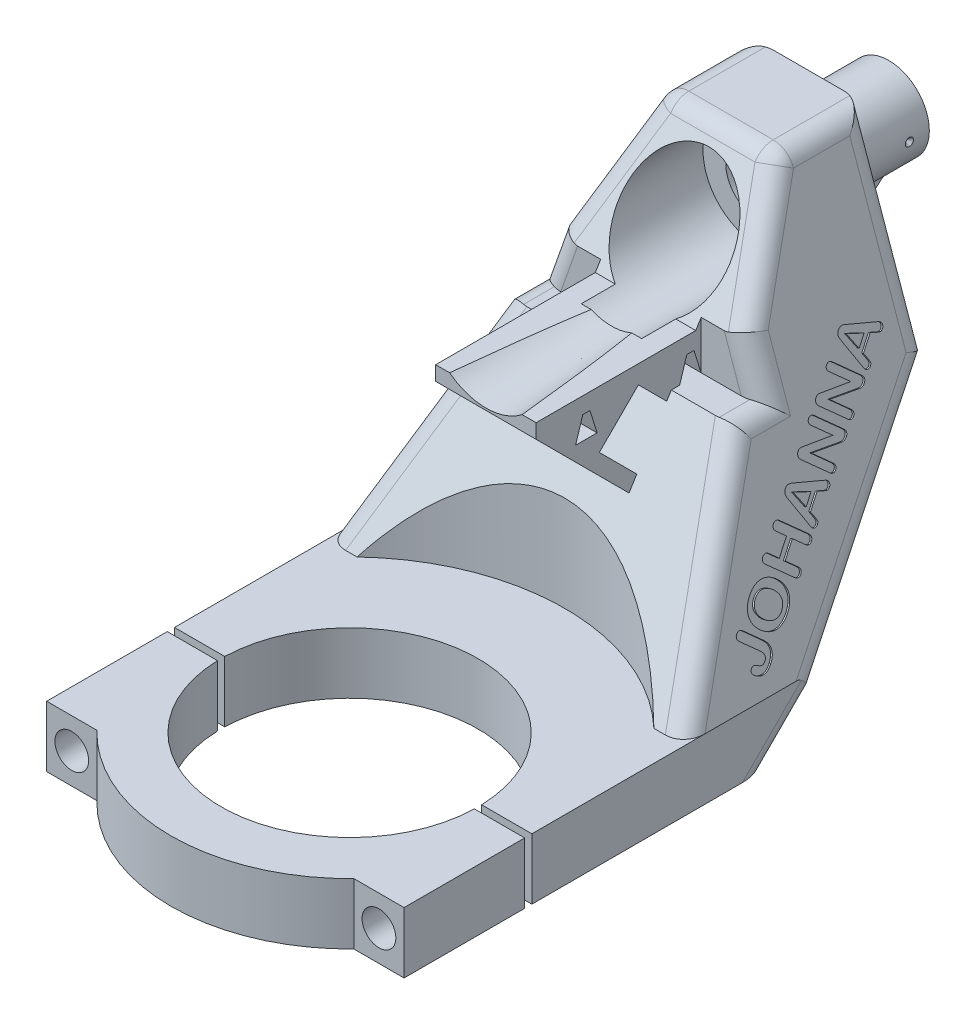
SolidWorks part; units mm, degrees
ref_plane "Front Plane" through (0, 0, 0) normal (0, 0, 1) x (1, 0, 0)
ref_plane "Top Plane" through (0, 0, 0) normal (0, 1, 0) x (1, 0, 0)
ref_plane "Right Plane" through (0, 0, 0) normal (1, 0, 0) x (0, 0, -1)
ref_plane "kitchenaid front" through (0, 0, -128) normal (0, 0, 1) x (1, 0, 0)
ref_plane "jar clamp bottom" through (0, -92.83, 0) normal (0, 1, 0) x (1, 0, 0)
sketch "Sketch1" plane through (0, -92.83, 0) normal (0, 1, 0) x (1, 0, 0)
  line L0 (49.81, -34.622) -> (49.81, 0)
  line L1 (49.81, -34.622) -> (35.81, -34.622)
  line L2 (0, -49.81) -> (0, -35.81)
  line L3 (49.81, 0) -> (49.81, 128)
  line L4 (0, 35.81) -> (0, 128)
  line L5 (0, 128) -> (49.81, 128)
  line L6 (35.81, 0) -> (35.81, -34.622) construction
  line L7 (-54.791, 128) -> (54.791, 128) construction
  arc A0 (0, -35.81) -> (0, 35.81) centre (0, 0) ccw
  arc A2 (49.81, 0) -> (0, 49.81) centre (0, 0) ccw construction
  arc A5 (35.81, -34.622) -> (49.81, 0) centre (0, 0) ccw construction
  arc A6 (35.81, -34.622) -> (49.81, 0) centre (0, 0) ccw construction
  arc A7 (0, -49.81) -> (35.81, -34.622) centre (0, 0) ccw
  dimension "D1" = 71.62
  dimension "D2" = 14
extrude "Boss-Extrude1" add sketch "Sketch1" along normal blind 17
ref_plane "Plane3" through (42.81, 0, 0) normal (1, 0, 0) x (0, 0, -1)
ref_plane "Plane4" through (0, -84.33, 0) normal (0, 1, 0) x (1, 0, 0)
ref_axis "Axis2" through (42.81, -84.33, -0.6811) along (0, 0, 1)
sketch "Sketch6" plane through (42.81, 0, 0) normal (1, 0, 0) x (0, 0, -1)
  line L0 (-34.622, -79.63) -> (-6, -79.63)
  line L1 (-34.622, -75.83) -> (-34.622, -92.83) construction
  line L2 (-6, -79.63) -> (-6, -82.13)
  line L3 (-6, -82.13) -> (-1, -82.13)
  line L4 (2, -82.13) -> (2, -82.73) construction
  line L5 (2, -82.73) -> (22, -82.73)
  line L6 (22, -82.73) -> (22, -84.33)
  line L7 (27.3955, -84.33) -> (-27.3955, -84.33) construction
  line L8 (22, -84.33) -> (-34.622, -84.33)
  line L9 (-34.622, -84.33) -> (-34.622, -79.63)
  line L10 (1, -82.13) -> (1, -64.33)
  line L11 (1, -64.33) -> (-1, -64.33)
  line L12 (-1, -64.33) -> (-1, -82.13)
  line L13 (-1, -82.13) -> (1, -82.13) construction
  line L14 (1, -82.13) -> (2, -82.13) construction
  line L16 (0, 9.35) -> (0, -9.35) construction
  line L17 (1, -82.13) -> (1, -82.73)
  line L18 (1, -82.73) -> (2, -82.73)
  point P18 (0, -64.33)
  dimension "D1" = 4.7
  dimension "D2" = 2.2
  dimension "D3" = 1.6
  dimension "D4" = 20
  dimension "D5" = 5
  dimension "D6" = 2
  dimension "D7" = 1
  dimension "D8" = 20
revolve "Cut-Revolve3" cut sketch "Sketch6" angle 360 about axis through (42.81, -84.33, -0.6811) along (0, 0, 1)
sketch "Sketch2" plane through (0, -92.83, 0) normal (0, 1, 0) x (1, 0, 0)
  line L0 (49.81, -34.622) -> (49.81, -1) construction
  line L1 (0, 128) -> (0, 35.81) construction
  line L2 (0, 60) -> (0, 128)
  line L3 (-9.35, 128) -> (9.35, 128) construction
  line L4 (0, 128) -> (49.81, 128)
  line L5 (49.81, 128) -> (49.81, 33.4509)
  arc A0 (49.81, 33.4509) -> (0, 60) centre (0, 0) ccw
  dimension "D1" = 60
extrude "Boss-Extrude2" add sketch "Sketch2" along normal offset from surface (112.83 mm away) 20 up to plane "Top Plane" offset beyond the face yes
sketch "Sketch3" plane through (0, 0, -128) normal (0, 0, 1) x (1, 0, 0)
  line L0 (0, 11.3) -> (0, 9.15)
  line L1 (0, 9.15) -> (0, -9.15) construction
  line L2 (0, -9.15) -> (0, -11.3)
  arc A0 (0, -11.3) -> (0, 11.3) centre (0, 0) ccw
  arc A1 (0, -9.15) -> (0, 9.15) centre (0, 0) ccw
  arc A2 (0, 11.3) -> (0, -11.3) centre (0, 0) ccw construction
  arc A3 (0, 9.15) -> (0, -9.15) centre (0, 0) ccw construction
  dimension "D1" = 18.3
  dimension "D2" = 22.6
extrude "Boss-Extrude3" add sketch "Sketch3" against normal blind 22.3
sketch "Sketch11" plane through (0, 0, 0) normal (1, 0, 0) x (0, 0, -1)
  line L0 (-49.6786, -34.03) -> (55, -34.03) construction
  line L1 (55, -34.03) -> (55, -92.83) construction
  line L2 (27.3955, -92.83) -> (-27.3955, -92.83) construction
  line L3 (63.7273, -13) -> (34.47, -13)
  line L5 (34.47, -13) -> (34.47, -13.5)
  line L6 (34.47, -13.5) -> (64.1074, -43.1374)
  line L8 (64.1074, -43.1374) -> (70.3979, -33.1815)
  line L9 (70.3979, -33.1815) -> (63.7273, -26.5109)
  line L11 (63.7273, -26.5109) -> (63.7273, -13)
  dimension "D1" = 58.8
  dimension "D2" = 55
  dimension "D3" = 45
  dimension "D4" = 0.5
extrude "Boss-Extrude6" add sketch "Sketch11" along normal up to surface (49.81 mm away) up to face at (49.81, -49.5533, -54.1503)
ref_axis "Axis1" through (0, 0, 59.6655) along (0, 0, -1)
sketch "Sketch4" plane through (0, 0, 0) normal (1, 0, 0) x (0, 0, -1)
  line L0 (114, 9.15) -> (114, 11.5)
  line L1 (-59.6655, 0) -> (157.1555, 0) construction
  line L2 (114, 11.5) -> (-16, 20)
  line L3 (-16, 20) -> (-16, 0)
  line L4 (-16, 0) -> (114, 0)
  line L5 (128, 27.3955) -> (128, -27.3955) construction
  line L6 (114, 9.15) -> (128, 9.15)
  line L7 (128, 9.15) -> (128, 0)
  line L8 (128, 0) -> (114, 0)
  line L9 (114, 0) -> (114, 9.15) construction
  dimension "D1" = 11.5
  dimension "D2" = 20
  dimension "D3" = 16
  dimension "D4" = 14
  dimension "D5" = 9.15
revolve "Cut-Revolve1" cut sketch "Sketch4" angle 360 about axis through (0, 0, 59.6655) along (0, 0, -1)
sketch "Sketch5" plane through (0, 0, 0) normal (1, 0, 0) x (0, 0, -1)
  line L0 (43.4509, -75.83) -> (63.897, -42.927)
  line L1 (33.4509, 20) -> (128, 20) construction
  line L2 (103, 20) -> (33.4509, 20)
  line L3 (33.4509, 20) -> (33.4509, -75.83)
  line L4 (33.4509, -75.83) -> (43.4509, -75.83)
  line L5 (128, 54.791) -> (128, -54.791) construction
  line L6 (1, -75.83) -> (33.4509, -75.83) construction
  line L7 (68.17, -92.83) -> (128, -33)
  line L8 (54.791, -92.83) -> (-54.791, -92.83) construction
  line L9 (128, -33) -> (128, -92.83)
  line L10 (128, -92.83) -> (68.17, -92.83)
  line L11 (38, -13) -> (82.4937, -13)
  line L12 (38, -13) -> (38, -17.03)
  line L13 (38, -17.03) -> (63.897, -42.927)
  line L14 (51, -17.5538) -> (49, -23.9536)
  line L15 (49, -23.9536) -> (55, -23.9536)
  line L16 (55, -23.9536) -> (53, -17.5538)
  line L17 (80, -17.5538) -> (78, -23.9536)
  line L18 (78, -23.9536) -> (84, -23.9536)
  line L19 (84, -23.9536) -> (82, -17.5538)
  line L20 (-59.6655, 0) -> (157.1555, 0) construction
  line L21 (63.897, -42.927) -> (82.4937, -13) construction
  line L22 (82.4937, -13) -> (103, 20)
  line L23 (52, -14.354) -> (81, -14.354) construction
  line L24 (37.4736, -16.5036) -> (60, -39.03) construction
  line L25 (52, -17.5538) -> (52, -23.9536) construction
  line L26 (52, -14.354) -> (52, -15.5538) construction
  line L27 (81, -17.5538) -> (81, -23.9536) construction
  line L28 (114, -11.5) -> (37.4736, -16.5036) construction
  line L29 (51, -17.5538) -> (53, -17.5538)
  line L30 (79.6639, -17.5538) -> (80, -17.5538) construction
  line L31 (80, -17.5538) -> (82, -17.5538)
  line L32 (53, -17.5538) -> (79.6639, -17.5538) construction
  line L33 (53, -17.5538) -> (52, -14.354) construction
  line L34 (52, -14.354) -> (52, -17.5538) construction
  line L35 (52, -14.354) -> (51, -17.5538) construction
  line L36 (82, -17.5538) -> (81, -14.354) construction
  line L37 (81, -14.354) -> (81, -17.5538) construction
  line L38 (81, -14.354) -> (80, -17.5538) construction
  line L39 (66.065, -39.4381) -> (55.6186, -28.9918)
  line L40 (55.6186, -28.9918) -> (66.5, -18.1104)
  line L41 (66.5, -18.1104) -> (74.4055, -26.0159)
  line L42 (74.4055, -26.0159) -> (66.065, -39.4381)
  dimension "D1" = 10
  dimension "D2" = 25
  dimension "D3" = 45
  dimension "D4" = 33
  dimension "D5" = 13
  dimension "D6" = 38
  dimension "D7" = 14
  dimension "D8" = 2
  dimension "D9" = 6
  dimension "D10" = 6
  dimension "D11" = 43
  dimension "D12" = 2
  dimension "D13" = 4
  dimension "D14" = 4
  dimension "D15" = 45
  dimension "D16" = 4
extrude "Cut-Extrude1" cut sketch "Sketch5" along normal through all
ref_plane "Plane7" through (0, 0, -53) normal (0, 0, 1) x (1, 0, 0)
sketch "Sketch16" plane through (0, 0, -53) normal (0, 0, 1) x (1, 0, 0)
  circle A0 centre (0, 0) radius 15.4885
  point P3 (0, -15.4885)
  point P7 (0, 0)
extrude "Cut-Extrude7" cut sketch "Sketch16" against normal up to surface (61 mm away) from offset 20 up to face at (5.1625, 0, -114) offset against normal yes
fillet "Fillet1" [suppressed] radius 5
sketch "Sketch7" plane through (0, 0, 0) normal (1, 0, 0) x (0, 0, -1)
  line L0 (130, -12.3) -> (130, -9.15)
  line L1 (130, -9.15) -> (150.3, -9.15)
  line L2 (150.3, -9.15) -> (128, -27.8619)
  line L3 (128, 54.791) -> (128, -54.791) construction
  line L4 (128, -27.8619) -> (128, -18.9782)
  line L5 (128, -18.9782) -> (130, -17.3)
  line L6 (130, -17.3) -> (130, -12.3)
  line L7 (150.3, -9.15) -> (114, -9.15) construction
  line L8 (150.3, -9.15) -> (150.3, -11.3) construction
  dimension "D1" = 50
  dimension "D2" = 2
  dimension "D3" = 5
extrude "Boss-Extrude5" add sketch "Sketch7" along normal blind 1 from offset 2
sketch "Sketch8" plane through (0, 0, 0) normal (0, 0, 1) x (1, 0, 0)
  line L0 (16, 20) -> (49.81, -75.83)
  line L1 (49.81, 20) -> (0, 20) construction
  line L2 (49.81, -75.83) -> (49.81, 20)
  line L3 (49.81, 20) -> (16, 20)
  line L4 (0, -49.1982) -> (0, -42.927) construction
  dimension "D1" = 16
extrude "Cut-Extrude2" cut sketch "Sketch8" against normal through all
sketch "Sketch9" plane through (0, -92.83, 0) normal (0, 1, 0) x (1, 0, 0)
  line L0 (0, -59.6655) -> (0, 157.1555) construction
  line L1 (0, 123) -> (0, 72) construction
  line L2 (-27.3955, 128) -> (27.3955, 128) construction
  circle A0 centre (0, 97.5) radius 25.5
  dimension "D1" = 5
  dimension "D2" = 12
extrude "Cut-Extrude3" [suppressed] cut sketch "Sketch9" along normal blind 70 from offset 6
chamfer "Chamfer1" [suppressed] distance 18 angle 45
sketch "Sketch10" plane through (0, 0, -38) normal (0, 0, 1) x (1, 0, 0)
  line L0 (31.5074, -23.9536) -> (0, -23.9536) construction
  line L1 (14, -9.0821) -> (63.6062, -9.0821)
  line L2 (14, -9.0821) -> (14, -23.9536)
  line L3 (14, -23.9536) -> (63.6062, -23.9536)
  line L4 (63.6062, -9.0821) -> (63.6062, -23.9536)
  line L5 (14, -9.0821) -> (63.6062, -23.9536) construction
  line L6 (14, -23.9536) -> (63.6062, -9.0821) construction
  point P4 (38.8031, -16.5178)
  dimension "D1" = 14
extrude "Cut-Extrude4" cut sketch "Sketch10" against normal blind 46
sketch "Sketch13" plane through (14, 0, 0) normal (1, 0, 0) x (0, 0, -1)
  line L0 (43.4509, -75.83) -> (85.7179, -7.8114)
  line L1 (103, 20) -> (84, -10.576) construction
  line L2 (85.7179, -7.8114) -> (5.4877, -7.8114)
  line L3 (5.4877, -7.8114) -> (43.4509, -75.83)
extrude "Cut-Extrude5" cut sketch "Sketch13" along normal through all
fillet "Fillet6" radius 6 9 edges at (40.6587, -49.8918, -59.569) (21.3938, 4.712, -93.5) (31.5074, -23.9536, -79.8436) (16, 20, -115.5) (25.3495, -6.5, -128) (42.2545, -54.415, -106.585) (49.81, -84.33, -76.67) (29.1475, -17.2648, -84) (8, 20, -103)
mirror "Mirror1" about plane through (0, 0, 0) normal (1, 0, 0) of bodies 116 107 106
ref_plane "Plane5" through (0, 0, -144.75) normal (0, 0, 1) x (1, 0, 0)
ref_axis "Axis3" through (-54.791, 0, -144.75) along (1, 0, 0)
sketch "Sketch12" plane through (0, 0, -144.75) normal (0, 0, 1) x (1, 0, 0)
  line L0 (10.15, 0) -> (13.15, 3)
  line L1 (-54.791, 0) -> (54.791, 0) construction
  line L2 (13.15, 3) -> (36.2885, 3)
  line L3 (36.2885, 3) -> (36.2885, 0)
  line L4 (36.2885, 0) -> (10.15, 0)
  circle A0 centre (0, 0) radius 9.15 construction
  point P6 (9.15, 0)
  dimension "D1" = 1
  dimension "D2" = 45
  dimension "D3" = 3
revolve "Cut-Revolve4" cut sketch "Sketch12" angle 360 about axis through (-54.791, 0, -144.75) along (1, 0, 0)
sketch "Sketch14" plane through (20.504, 7.2341, 0) normal (0.943, 0.3327, 0) x (0, 0, -1)
  line L0 (63.6923, -88.0822) -> (122, -26.252) construction
  line L1 (74.6884, -88.0822) -> (49.2745, -88.0822) construction
  line L3 (74.6884, -88.0822) -> (122, -37.9124) construction
  line L4 (122, -37.9124) -> (122, 9.2916) construction
  text T0 "JOHANNA" font "Arial Rounded MT Bold" height 11
  dimension "D1" = 8
extrude "Cut-Extrude6" cut sketch "Sketch14" against normal blind 0.5
ref_plane "Plane6" through (-14, -17.5538, -53) normal (-1, 0, 0) x (0, 0, 1)
